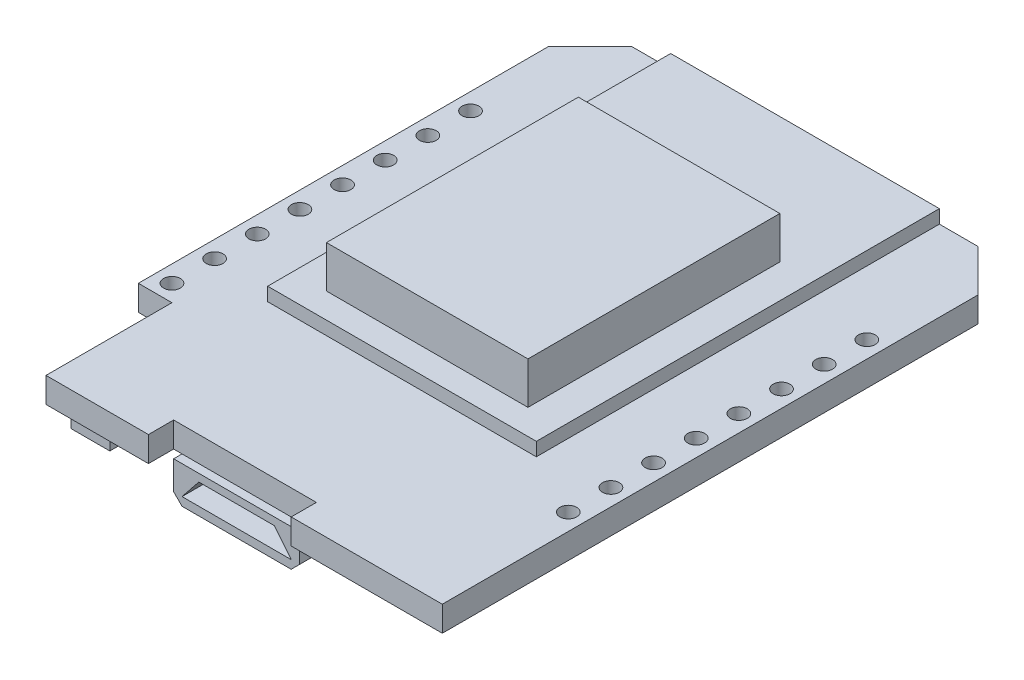
SolidWorks part; units mm, degrees
note: The reader was unsure of these and kept them because the rebuilt part matched: shared geometry of "Sketch5<4>", "Sketch5<5>", "Sketch5<6>".
other "USB Micro"
other "PCB"
ref_plane "Front Plane" through (0, 0, 0) normal (0, 0, 1) x (1, 0, 0)
ref_plane "Top Plane" through (0, 0, 0) normal (0, 1, 0) x (1, 0, 0)
ref_plane "Right Plane" through (0, 0, 0) normal (1, 0, 0) x (0, 0, -1)
sketch "Sketch1" plane through (0, 0, 0) normal (0, 1, 0) x (1, 0, 0)
  line L0 (0, 0) -> (0, 31.9)
  line L1 (0, 31.9) -> (-2.5, 34.4)
  line L2 (-2.5, 34.4) -> (-23.1, 34.4)
  line L3 (-23.1, 34.4) -> (-25.6, 31.9)
  line L4 (-25.6, 31.9) -> (-25.6, 7.5)
  line L5 (-25.6, 7.5) -> (-23.6, 7.5)
  line L6 (-23.6, 7.5) -> (-23.6, 0)
  line L7 (0, 0) -> (-9, 0)
  line L8 (-9, 0) -> (-9, 1.5)
  line L9 (-9, 1.5) -> (-17.5, 1.5)
  line L10 (-17.5, 1.5) -> (-17.5, 0)
  line L11 (-17.5, 0) -> (-23.6, 0)
  line L12 (-1, -1.7092) -> (-1, 37.7939) construction
  line L13 (-24.6, 37.7939) -> (-24.6, -1.7092) construction
  line L14 (-28.0763, 8.5) -> (2.6406, 8.5) construction
  circle A0 centre (-24.6, 8.5) radius 0.5
  circle A1 centre (-1, 8.5) radius 0.5
  circle A2 centre (-24.6, 11.04) radius 0.5
  circle A3 centre (-1, 11.04) radius 0.5
  circle A4 centre (-24.6, 13.58) radius 0.5
  circle A5 centre (-1, 13.58) radius 0.5
  circle A6 centre (-24.6, 16.12) radius 0.5
  circle A7 centre (-1, 16.12) radius 0.5
  circle A8 centre (-24.6, 18.66) radius 0.5
  circle A9 centre (-1, 18.66) radius 0.5
  circle A10 centre (-24.6, 21.2) radius 0.5
  circle A11 centre (-1, 21.2) radius 0.5
  circle A12 centre (-24.6, 23.74) radius 0.5
  circle A13 centre (-1, 23.74) radius 0.5
  circle A14 centre (-24.6, 26.28) radius 0.5
  circle A15 centre (-1, 26.28) radius 0.5
  dimension "D13" = 1
  dimension "D1" = 25.6
  dimension "D2" = 34.4
  dimension "D3" = 2.5
  dimension "D4" = 2.5
  dimension "D5" = 7.5
  dimension "D6" = 2
  dimension "D7" = 8.5
  dimension "D8" = 1.5
  dimension "D9" = 9
  dimension "D10" = 1
  dimension "D11" = 1
  dimension "D12" = 8.5
  dimension "D14" = 8
extrude "PCB" add sketch "Sketch1" along normal blind 1.5
sketch "Sketch2" plane through (0, 1.5, 0) normal (0, 1, 0) x (1, 0, 0)
  line L0 (-2.5, 34.4) -> (-23.1, 34.4) construction
  line L1 (-20.8, 34.4) -> (-4.8, 34.4)
  line L2 (-20.8, 34.4) -> (-20.8, 10.4)
  line L3 (-20.8, 10.4) -> (-4.8, 10.4)
  line L4 (-4.8, 34.4) -> (-4.8, 10.4)
  point P6 (-12.8, 34.4)
  point P7 (-12.8, 34.4)
  point P8 (-12.8, 34.4)
  point P9 (-12.8, 34.4)
  point P10 (-12.8, 34.4)
  point P11 (-12.8, 34.4)
  point P12 (-4.8, 31.3326)
  dimension "D1" = 24
  dimension "D2" = 16
extrude "ESP8266 PCB" add sketch "Sketch2" along normal blind 0.8 separate body
sketch "Sketch3" plane through (0, 2.3, 0) normal (0, 1, 0) x (1, 0, 0)
  line L0 (-4.8, 34.4) -> (-20.8, 34.4) construction
  line L1 (-18.8, 11.9) -> (-6.8, 11.9)
  line L2 (-18.8, 11.9) -> (-18.8, 26.9)
  line L3 (-18.8, 26.9) -> (-6.8, 26.9)
  line L4 (-6.8, 11.9) -> (-6.8, 26.9)
  point P4 (-12.8, 34.4)
  point P5 (-12.8, 26.9)
  dimension "D1" = 12
  dimension "D2" = 15
  dimension "D3" = 7.5
extrude "ESP8266 Rf Shield" add sketch "Sketch3" along normal blind 2.5 separate body
sketch "Sketch5" plane through (0, 0, 0) normal (0, -1, 0) x (1, 0, 0)
  line L0 (-23.6, -7.5) -> (-23.6, 0) construction
  line L1 (-23.6, -1.5) -> (-21.3, -1.5)
  line L2 (-23.6, -1.5) -> (-23.6, -6)
  line L3 (-23.6, -6) -> (-21.3, -6)
  line L4 (-21.3, -1.5) -> (-21.3, -6)
  line L5 (-3.9144, -3.7056) -> (-2.4144, -3.7056)
  line L6 (-17, -1) -> (-9.5, -1)
  line L7 (-17, -1) -> (-17, -6.6)
  line L8 (-17, -6.6) -> (-9.5, -6.6)
  line L9 (-9.5, -1) -> (-9.5, -6.6)
  line L10 (-3.9144, -3.7056) -> (-3.9144, -2.7056)
  line L11 (-18.7643, -9.825) -> (-8.6486, -9.825)
  line L12 (-18.7643, -9.825) -> (-18.7643, -14.4)
  line L13 (-18.7643, -14.4) -> (-8.6486, -14.4)
  line L14 (-8.6486, -9.825) -> (-8.6486, -14.4)
  line L15 (-2.5, -34.4) -> (-23.1, -34.4) construction
  line L16 (-20.1, -28.4) -> (-18.6, -28.4)
  line L17 (-20.1, -28.4) -> (-20.1, -27.4)
  line L18 (-20.1, -27.4) -> (-18.6, -27.4)
  line L19 (-3.9144, -2.7056) -> (-2.4144, -2.7056)
  line L20 (-2.4144, -3.7056) -> (-2.4144, -2.7056)
  line L21 (-6.0768, -10.9216) -> (-6.0768, -9.4216)
  line L22 (-6.0768, -10.9216) -> (-7.0768, -10.9216)
  line L23 (-7.0768, -10.9216) -> (-7.0768, -9.4216)
  line L24 (-6.0768, -9.4216) -> (-7.0768, -9.4216)
  line L25 (-4.477, -10.9216) -> (-4.477, -9.4216)
  line L26 (-4.477, -10.9216) -> (-5.477, -10.9216)
  line L27 (-5.477, -10.9216) -> (-5.477, -9.4216)
  line L28 (-4.477, -9.4216) -> (-5.477, -9.4216)
  line L29 (-7.3592, -3.3369) -> (-7.3592, -1.8369)
  line L30 (-7.3592, -3.3369) -> (-8.3592, -3.3369)
  line L31 (-17.5, -1.5) -> (-9, -1.5) construction
  line L32 (-18.6, -28.4) -> (-18.6, -27.4)
  line L33 (-25.6, -31.9) -> (-25.6, -7.5) construction
  line L34 (-13.6, -28.4) -> (-12.1, -28.4)
  line L35 (-13.6, -28.4) -> (-13.6, -27.4)
  line L36 (-13.6, -27.4) -> (-12.1, -27.4)
  line L37 (-12.1, -28.4) -> (-12.1, -27.4)
  line L38 (-7.1, -28.4) -> (-5.6, -28.4)
  line L39 (-7.1, -28.4) -> (-7.1, -27.4)
  line L40 (-7.1, -27.4) -> (-5.6, -27.4)
  line L41 (-5.6, -28.4) -> (-5.6, -27.4)
  line L42 (-13.6, -26.4) -> (-12.1, -26.4) [skipped]
  line L43 (-13.6, -26.4) -> (-13.6, -25.4) [skipped]
  line L44 (-13.6, -25.4) -> (-12.1, -25.4) [skipped]
  line L45 (-12.1, -26.4) -> (-12.1, -25.4) [skipped]
  line L46 (-7.1, -26.4) -> (-5.6, -26.4)
  line L47 (-7.1, -26.4) -> (-7.1, -25.4)
  line L48 (-7.1, -25.4) -> (-5.6, -25.4)
  line L49 (-5.6, -26.4) -> (-5.6, -25.4)
  line L50 (-13.6, -24.4) -> (-12.1, -24.4)
  line L51 (-13.6, -24.4) -> (-13.6, -23.4)
  line L52 (-13.6, -23.4) -> (-12.1, -23.4)
  line L53 (-12.1, -24.4) -> (-12.1, -23.4)
  line L54 (-7.1, -24.4) -> (-5.6, -24.4) [skipped]
  line L55 (-7.1, -24.4) -> (-7.1, -23.4) [skipped]
  line L56 (-7.1, -23.4) -> (-5.6, -23.4) [skipped]
  line L57 (-5.6, -24.4) -> (-5.6, -23.4) [skipped]
  line L58 (-13.6, -22.4) -> (-12.1, -22.4)
  line L59 (-13.6, -22.4) -> (-13.6, -21.4)
  line L60 (-13.6, -21.4) -> (-12.1, -21.4)
  line L61 (-12.1, -22.4) -> (-12.1, -21.4)
  line L62 (-7.1, -22.4) -> (-5.6, -22.4) [skipped]
  line L63 (-7.1, -22.4) -> (-7.1, -21.4) [skipped]
  line L64 (-7.1, -21.4) -> (-5.6, -21.4) [skipped]
  line L65 (-5.6, -22.4) -> (-5.6, -21.4) [skipped]
  line L66 (-13.6, -20.4) -> (-12.1, -20.4) [skipped]
  line L67 (-13.6, -20.4) -> (-13.6, -19.4) [skipped]
  line L68 (-13.6, -19.4) -> (-12.1, -19.4) [skipped]
  line L69 (-12.1, -20.4) -> (-12.1, -19.4) [skipped]
  line L70 (-7.1, -20.4) -> (-5.6, -20.4)
  line L71 (-7.1, -20.4) -> (-7.1, -19.4)
  line L72 (-7.1, -19.4) -> (-5.6, -19.4)
  line L73 (-5.6, -20.4) -> (-5.6, -19.4)
  line L74 (-13.6, -18.4) -> (-12.1, -18.4)
  line L75 (-13.6, -18.4) -> (-13.6, -17.4)
  line L76 (-13.6, -17.4) -> (-12.1, -17.4)
  line L77 (-12.1, -18.4) -> (-12.1, -17.4)
  line L78 (-7.1, -18.4) -> (-5.6, -18.4)
  line L79 (-7.1, -18.4) -> (-7.1, -17.4)
  line L80 (-7.1, -17.4) -> (-5.6, -17.4)
  line L81 (-5.6, -18.4) -> (-5.6, -17.4)
  line L82 (-13.6, -16.4) -> (-12.1, -16.4) [skipped]
  line L83 (-13.6, -16.4) -> (-13.6, -15.4) [skipped]
  line L84 (-13.6, -15.4) -> (-12.1, -15.4) [skipped]
  line L85 (-12.1, -16.4) -> (-12.1, -15.4) [skipped]
  line L86 (-7.1, -16.4) -> (-5.6, -16.4)
  line L87 (-7.1, -16.4) -> (-7.1, -15.4)
  line L88 (-7.1, -15.4) -> (-5.6, -15.4)
  line L89 (-5.6, -16.4) -> (-5.6, -15.4)
  line L90 (-13.6, -14.4) -> (-12.1, -14.4) [skipped]
  line L91 (-13.6, -14.4) -> (-13.6, -13.4) [skipped]
  line L92 (-13.6, -13.4) -> (-12.1, -13.4) [skipped]
  line L93 (-12.1, -14.4) -> (-12.1, -13.4) [skipped]
  line L94 (-7.1, -14.4) -> (-5.6, -14.4)
  line L95 (-7.1, -14.4) -> (-7.1, -13.4)
  line L96 (-7.1, -13.4) -> (-5.6, -13.4)
  line L97 (-5.6, -14.4) -> (-5.6, -13.4)
  line L98 (-20.1, -26.4) -> (-18.6, -26.4)
  line L99 (-20.1, -26.4) -> (-20.1, -25.4)
  line L100 (-20.1, -25.4) -> (-18.6, -25.4)
  line L101 (-18.6, -26.4) -> (-18.6, -25.4)
  line L102 (-20.1, -24.4) -> (-18.6, -24.4)
  line L103 (-20.1, -24.4) -> (-20.1, -23.4)
  line L104 (-20.1, -23.4) -> (-18.6, -23.4)
  line L105 (-18.6, -24.4) -> (-18.6, -23.4)
  line L106 (-20.1, -22.4) -> (-18.6, -22.4)
  line L107 (-20.1, -22.4) -> (-20.1, -21.4)
  line L108 (-20.1, -21.4) -> (-18.6, -21.4)
  line L109 (-18.6, -22.4) -> (-18.6, -21.4)
  line L110 (-20.1, -20.4) -> (-18.6, -20.4)
  line L111 (-20.1, -20.4) -> (-20.1, -19.4)
  line L112 (-20.1, -19.4) -> (-18.6, -19.4)
  line L113 (-18.6, -20.4) -> (-18.6, -19.4)
  line L114 (-20.1, -18.4) -> (-18.6, -18.4)
  line L115 (-20.1, -18.4) -> (-20.1, -17.4)
  line L116 (-20.1, -17.4) -> (-18.6, -17.4)
  line L117 (-18.6, -18.4) -> (-18.6, -17.4)
  line L118 (-20.1, -16.4) -> (-18.6, -16.4)
  line L119 (-20.1, -16.4) -> (-20.1, -15.4)
  line L120 (-20.1, -15.4) -> (-18.6, -15.4)
  line L121 (-18.6, -16.4) -> (-18.6, -15.4)
  line L122 (-20.1, -14.4) -> (-18.6, -14.4) [skipped]
  line L123 (-20.1, -14.4) -> (-20.1, -13.4) [skipped]
  line L124 (-20.1, -13.4) -> (-18.6, -13.4) [skipped]
  line L125 (-18.6, -14.4) -> (-18.6, -13.4) [skipped]
  line L126 (-23.6, 0) -> (-17.5, 0) construction
  line L127 (-8.3592, -3.3369) -> (-8.3592, -1.8369)
  line L128 (-7.3592, -1.8369) -> (-8.3592, -1.8369)
  line L129 (-5.4144, -1.8369) -> (-3.9144, -1.8369)
  line L130 (-5.4144, -1.8369) -> (-5.4144, -0.8369)
  line L131 (-5.4144, -0.8369) -> (-3.9144, -0.8369)
  line L132 (-3.9144, -1.8369) -> (-3.9144, -0.8369)
  line L133 (-7.2524, -7.3947) -> (-7.2524, -5.8947)
  line L134 (-7.2524, -7.3947) -> (-8.2524, -7.3947)
  line L135 (-8.2524, -7.3947) -> (-8.2524, -5.8947)
  line L136 (-7.2524, -5.8947) -> (-8.2524, -5.8947)
  line L137 (-4.3695, -7.2325) -> (-2.8695, -7.2325)
  line L138 (-4.3695, -7.2325) -> (-4.3695, -6.2325)
  line L139 (-4.3695, -6.2325) -> (-2.8695, -6.2325)
  line L140 (-2.8695, -7.2325) -> (-2.8695, -6.2325)
  line L141 (-18.357, -8.0394) -> (-18.357, -5.3089)
  line L142 (-18.357, -8.0394) -> (-19.357, -8.0394)
  line L143 (-19.357, -8.0394) -> (-19.357, -5.3089)
  line L144 (-18.357, -5.3089) -> (-19.357, -5.3089)
  line L145 (-9, 0) -> (0, 0) construction
  line L146 (-20.1, -28.4) -> (-13.6, -28.4) construction
  line L147 (-20.1, -28.4) -> (-20.1, -26.4) construction
  point P38 (-13.25, -1.5)
  point P131 (-13.25, -1)
  point P132 (-13.25, -1.5)
  dimension "D1" = 1.5
  dimension "D2" = 1
  dimension "D3" = 6
  dimension "D4" = 5.5
  dimension "D6" = 2.3
  dimension "D7" = 4.5
  dimension "D8" = 1.5
  dimension "D9" = 8
  dimension "D10" = 7.5
  dimension "D11" = 5.6
  dimension "D12" = 90
  dimension "D13" = 6.5
  dimension "D14" = 2
  dimension "D5" = 3
extrude "Boss-Extrude4" add sketch "Sketch5" along normal blind 2.2 separate body contours L7 L8 L9 L6
chamfer "Chamfer1" distance 0.5 angle 45 2 edges at (-9.5, -2.2, -3.8) (-17, -2.2, -3.8)
sketch "Sketch12" plane through (0, 0, -1) normal (0, 0, 1) x (1, 0, 0)
  line L0 (-15.5, -0.45) -> (-11, -0.45)
  line L1 (-11, -0.45) -> (-10, -1.7)
  line L2 (-10, -1.7) -> (-16.5, -1.7)
  line L3 (-16.5, -1.7) -> (-15.5, -0.45)
  line L4 (-17, 0) -> (-9.5, 0) construction
  line L5 (-16.5, -2.2) -> (-10, -2.2) construction
  line L6 (-9.5, -1.7) -> (-9.5, 0) construction
  point P2 (-13.25, -0.45)
  point P5 (-13.25, 0)
  point P6 (-13.25, -1.7)
  point P9 (-13.25, -2.2)
  dimension "D1" = 0.5
  dimension "D2" = 1.5
  dimension "D3" = 0.5
  dimension "D4" = 1.75
extrude "Cut-Extrude1" cut sketch "Sketch12" against normal blind 4 from surface at 0 starting at face at (-13.25, -1.3, -1)
extrude "Button Body" add sketch "Sketch5<4>" along normal blind 2 from surface at 0 separate body starting at face at (-24.6, 0, -25.78)
sketch "Sketch5<4>" plane through (0, 0, 0) normal (0, -1, 0) x (1, 0, 0) same geometry as "Sketch5"
sketch "Sketch11" plane through (-23.6, 0, 0) normal (-1, 0, 0) x (0, 0, 1)
  line L0 (-6, -2) -> (-1.5, 0) construction
  line L1 (-6, 0) -> (-1.5, -2) construction
  line L2 (-7.5, 0) -> (0, 0) construction
  line L3 (-4.75, -1.4475) -> (-2.75, -1.4475)
  line L4 (-4.75, -1.4475) -> (-4.75, -0.5525)
  line L5 (-4.75, -0.5525) -> (-2.75, -0.5525)
  line L6 (-2.75, -1.4475) -> (-2.75, -0.5525)
  line L7 (-4.75, -1.4475) -> (-2.75, -0.5525) construction
  line L8 (-4.75, -0.5525) -> (-2.75, -1.4475) construction
  line L9 (-6, 0) -> (-1.5, 0) construction
  point P8 (-3.75, -1)
  point P9 (-3.75, -1)
  dimension "D1" = 2
  dimension "D2" = 0.5525
  dimension "D3" = 1.25
  dimension "D4" = 1
  dimension "D5" = 2
extrude "Button Actuator" add sketch "Sketch11" along normal blind 1 separate body
extrude "Components1" add sketch "Sketch5<5>" along normal blind 1 from surface at 0 separate body contours L5 L20 L19 L10 | L14 L11 L12 L13 | L34 L37 L36 L35 | L74 L77 L76 L75 | L29 L128 L127 L30 starting at face at (-24.6, 0, -25.78)
sketch "Sketch5<5>" plane through (0, 0, 0) normal (0, -1, 0) x (1, 0, 0) same geometry as "Sketch5"
extrude "Components 2" add sketch "Sketch5<6>" along normal blind 0.5 from surface at 0 separate body contours L118 L121 L120 L119 | L114 L117 L116 L115 | L110 L113 L112 L111 | L106 L109 L108 L107 | L102 L105 L104 L103 | L98 L101 L100 L99 | L16 L32 L18 L17 | L50 L53 L52 L51 | L58 L61 L60 L59 | L141 L144 L143 L142 | L129 L132 L131 L130 | L133 L136 L135 L134 | L137 L140 L139 L138 | L25 L28 L27 L26 | L21 L24 L23 L22 | L94 L97 L96 L95 | L86 L89 L88 L87 | L78 L81 L80 L79 | L70 L73 L72 L71 | L46 L49 L48 L47 | L38 L41 L40 L39 starting at face at (-24.6, 0, -25.78)
sketch "Sketch5<6>" plane through (0, 0, 0) normal (0, -1, 0) x (1, 0, 0) same geometry as "Sketch5"
